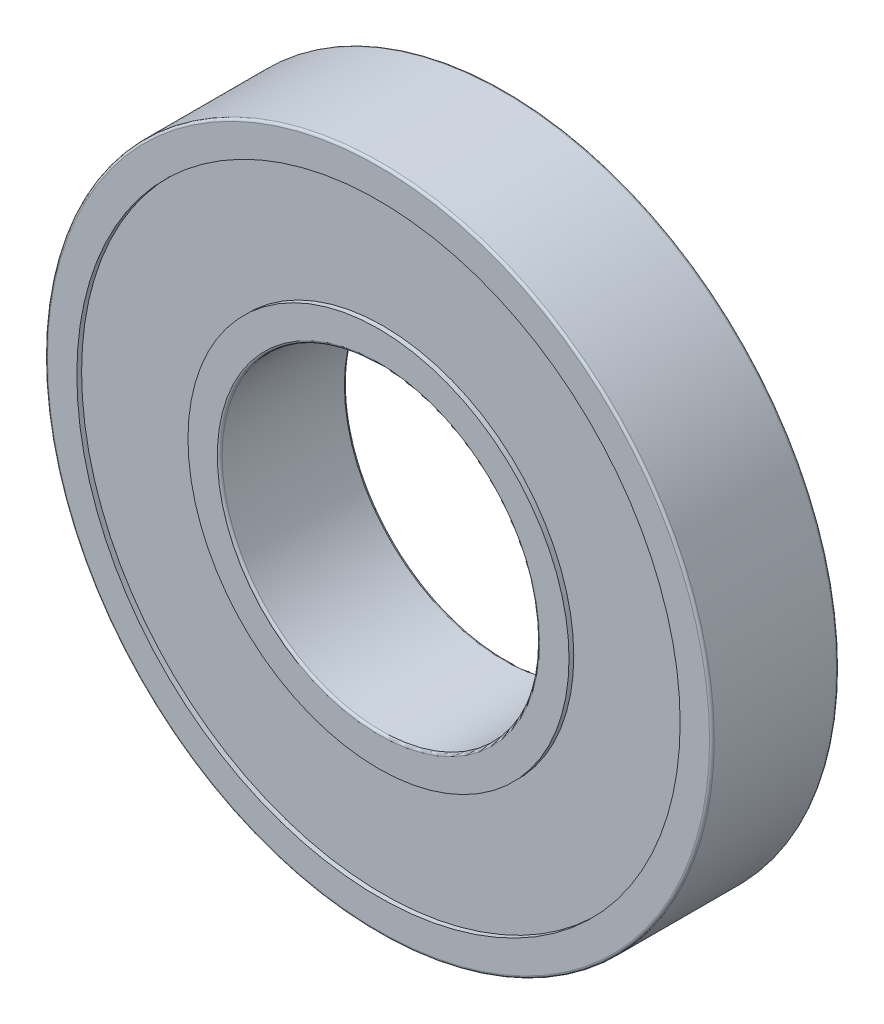
SolidWorks part; units mm, degrees
ref_plane "Front Plane" through (0, 0, 0) normal (0, 0, 1) x (1, 0, 0)
ref_plane "Top Plane" through (0, 0, 0) normal (0, 1, 0) x (1, 0, 0)
ref_plane "Right Plane" through (0, 0, 0) normal (1, 0, 0) x (0, 0, -1)
sketch "Sketch1" plane through (0, 0, 0) normal (0, 0, 1) x (1, 0, 0)
  circle A0 centre (0, 0) radius 10
  circle A1 centre (0, 0) radius 21
  dimension "D1" = 20
  dimension "D2" = 42
extrude "Boss-Extrude1" add sketch "Sketch1" along normal blind 8
sketch "Sketch2" plane through (0, 0, 8) normal (0, 0, 1) x (1, 0, 0)
  circle A3 centre (0, 0) radius 19
  circle A6 centre (0, 0) radius 12
  dimension "D1" = 24
  dimension "D2" = 38
extrude "Cut-Extrude1" cut sketch "Sketch2" against normal blind 0.3
extrude "Cut-Extrude2" cut sketch "Sketch2<2>" along normal blind 0.5 from surface starting at face at (21, 0, 0)
sketch "Sketch2<2>" plane through (0, 0, 8) normal (0, 0, 1) x (1, 0, 0) same geometry as "Sketch2"
fillet "Fillet1" radius 0.15 4 edges at (10, 0, 8) (21, 0, 8) (10, 0, 0) (21, 0, 0)
